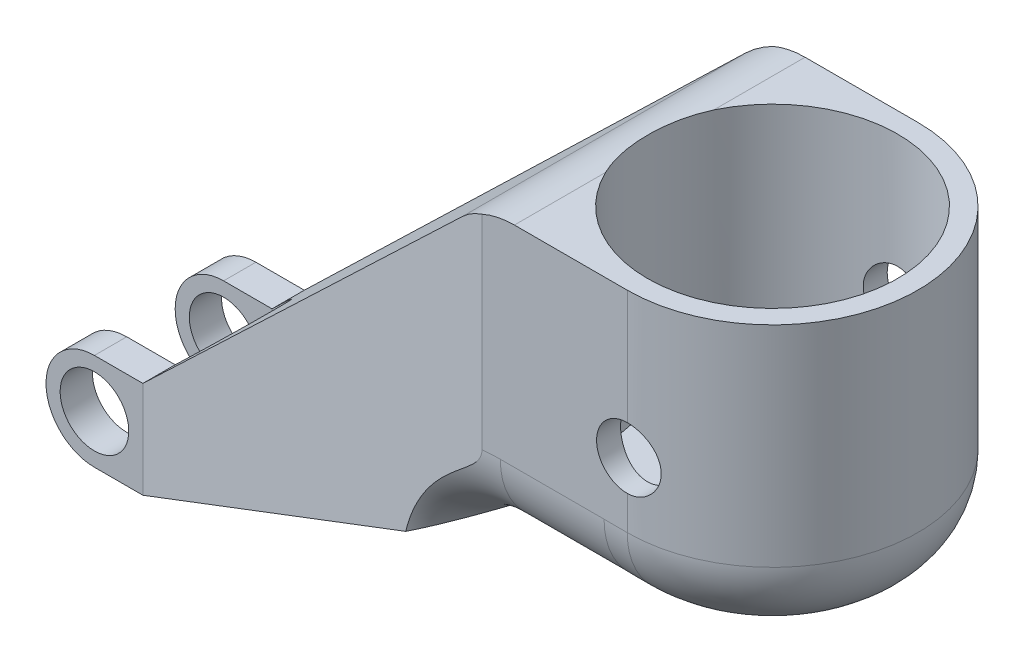
SolidWorks part; units mm, degrees
ref_plane "Front Plane" through (0, 0, 0) normal (0, 0, 1) x (1, 0, 0)
ref_plane "Top Plane" through (0, 0, 0) normal (0, 1, 0) x (1, 0, 0)
ref_plane "Right Plane" through (0, 0, 0) normal (1, 0, 0) x (0, 0, -1)
sketch "Sketch1" plane through (0, 0, 0) normal (0, 1, 0) x (1, 0, 0)
  circle A0 centre (0, 0) radius 9
  circle A1 centre (0, 0) radius 4.25
  dimension "D1" = 18
  dimension "D2" = 8.5
extrude "Boss-Extrude1" add sketch "Sketch1" along normal blind 18
sketch "Sketch3" plane through (0, 0, 0) normal (0, 0, 1) x (1, 0, 0)
  line L1 (-9, 9.7529) -> (-9, 0) construction
  spline S0 degree 2 poles (-9, 9.7529) (-16.3465, -4.552) (-32, -8.681) knots 0 0 0 1 1 1
  dimension "D1" = 23
ref_plane "Plane1" through (-34, 0, 0) normal (1, 0, 0) x (0, 0, -1)
ref_plane "Plane2" through (-9, 0, 0) normal (1, 0, 0) x (0, 0, -1)
sketch "Sketch7" plane through (-9, 0, 0) normal (1, 0, 0) x (0, 0, -1)
  line L0 (-9, 18) -> (9, 0) construction
  line L2 (-9, 0) -> (9, 0)
  line L3 (-9, 0) -> (-9, 18)
  line L4 (-9, 18) -> (9, 18)
  line L5 (9, 0) -> (9, 18)
  line L6 (-9, 0) -> (9, 18) construction
  line L7 (-9, 18) -> (9, 0) construction
  point P4 (0, 9)
sketch "Sketch9" plane through (-34, 0, 0) normal (1, 0, 0) x (0, 0, -1)
  line L1 (-5, -6) -> (5, -6)
  line L2 (-5, -6) -> (-5, -12)
  line L3 (-5, -12) -> (5, -12)
  line L4 (5, -6) -> (5, -12)
  line L5 (-5, -6) -> (5, -12) construction
  line L6 (-5, -12) -> (5, -6) construction
  line L7 (0, 11.8112) -> (0, -18.857) construction
  point P0 (0, -9)
  dimension "D1" = 10
  dimension "D2" = 6
  dimension "D3" = 18
loft "Loft12" add profiles "Sketch7", "Sketch9" connector at (-9, 0, 9) connector at (-34, -12, 5)
sketch "Sketch11" plane through (-9, 0, 0) normal (1, 0, 0) x (0, 0, -1)
  line L1 (-9, 0) -> (9, 0)
  line L2 (-9, 0) -> (-9, 18)
  line L3 (-9, 18) -> (9, 18)
  line L4 (9, 0) -> (9, 18)
  line L5 (-9, 0) -> (9, 18) construction
  line L6 (-9, 18) -> (9, 0) construction
  point P0 (0, 9)
extrude "Boss-Extrude2" add sketch "Sketch11" along normal blind 9
sketch "Sketch12" plane through (0, 0, 0) normal (0, -1, 0) x (1, 0, 0)
  circle A0 centre (0, 0) radius 4.25
extrude "Cut-Extrude3" cut sketch "Sketch12" against normal through all both and the other way through all
sketch "Sketch13" plane through (-34, 0, 0) normal (-1, 0, 0) x (0, 0, 1)
  line L0 (5, -12) -> (-5, -12) construction
  line L1 (5, -6) -> (3, -6)
  line L2 (5, -6) -> (5, -12)
  line L3 (5, -12) -> (3, -12)
  line L4 (3, -6) -> (3, -12)
  line L5 (0, -4.8047) -> (0, -12.4555) construction
  line L6 (0, -8.681) -> (0, 9.7529) construction
  line L7 (-5, -12) -> (-3, -12)
  line L8 (-3, -6) -> (-3, -12)
  line L9 (-5, -6) -> (-3, -6)
  line L10 (-5, -6) -> (-5, -12)
  dimension "D1" = 6
extrude "Boss-Extrude3" add sketch "Sketch13" along normal blind 6
sketch "Sketch14" plane through (0, 0, 5) normal (0, 0, 1) x (1, 0, 0)
  line L0 (-40, -6) -> (-34, -12) construction
  circle A0 centre (-37, -9) radius 2.125
  dimension "D1" = 4.25
extrude "Cut-Extrude4" cut sketch "Sketch14" against normal through all both and the other way through all
sketch "Sketch2" plane through (0, 18, 0) normal (0, 1, 0) x (1, 0, 0)
  circle A0 centre (0, 0) radius 7.75
  dimension "D1" = 15.5
extrude "Cut-Extrude1" cut sketch "Sketch2" against normal blind 15
fillet "Fillet1" radius 3 4 edges at (-40, -12, -4) (-40, -6, -4) (-40, -6, 4) (-40, -12, 4)
sketch "Sketch15" plane through (0, 0, 0) normal (0, 1, 0) x (1, 0, 0)
  line L0 (-34, 3) -> (-34, -3) construction
  circle A0 centre (-34, 0) radius 3
fillet "Fillet3" radius 5 2 edges
fillet "Fillet4" radius 5 4 edges at (-8.4348, -0.0329, 9) (-8.4348, -0.0329, -9)
extrude "Cut-Extrude6" cut sketch "Sketch15" against normal through all both and the other way through all contours A0
sketch "Sketch17" plane through (0, 0, 0) normal (0, 0, 1) x (1, 0, 0)
  line L0 (0, 18) -> (0, 0) construction
  circle A0 centre (0, 9) radius 1.9
  dimension "D1" = 3.8
extrude "Cut-Extrude7" cut sketch "Sketch17" against normal through all both and the other way through all
